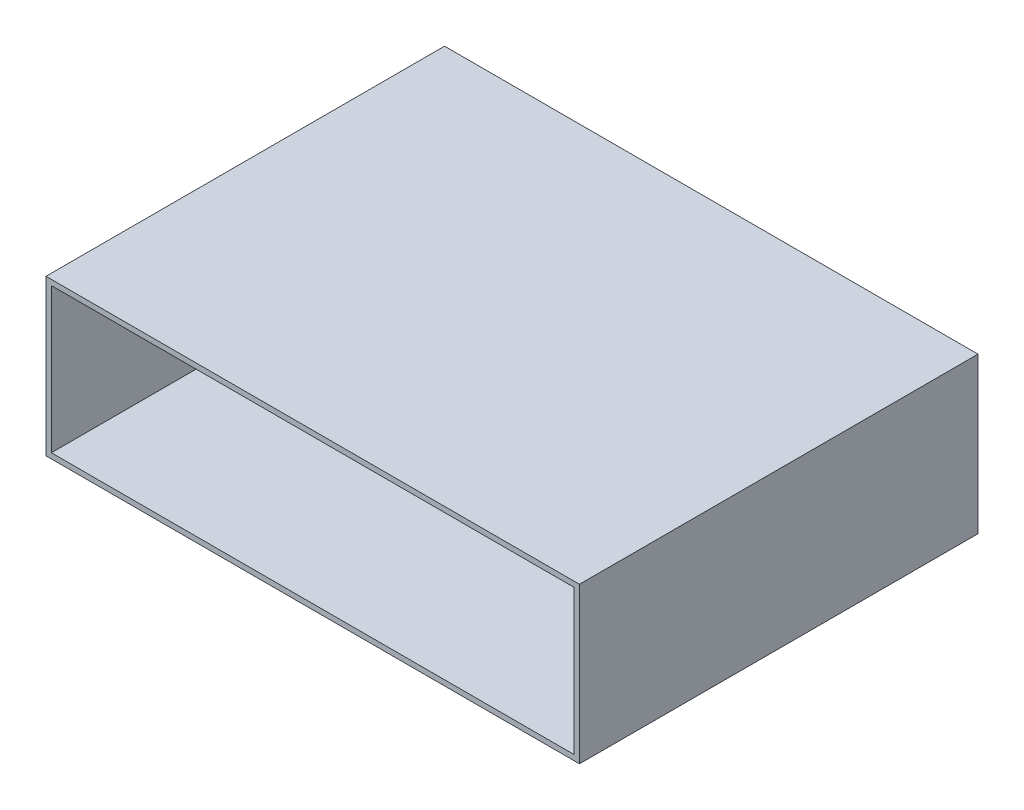
SolidWorks part; units mm, degrees
material "Custom Plastic"
ref_plane "X-Y Datum" through (0, 0, 0) normal (0, 0, 1) x (1, 0, 0)
ref_plane "X-Z Datum" through (0, 0, 0) normal (0, 1, 0) x (1, 0, 0)
ref_plane "Y-Z Datum" through (0, 0, 0) normal (1, 0, 0) x (0, 0, -1)
sketch "Sketch1" plane through (0, 0, 0) normal (0, 0, 1) x (1, 0, 0)
  line L1 (-154.6125, -42.825) -> (154.6125, -42.825)
  line L2 (-154.6125, -42.825) -> (-154.6125, 42.825)
  line L3 (-154.6125, 42.825) -> (154.6125, 42.825)
  line L4 (154.6125, -42.825) -> (154.6125, 42.825)
  line L5 (-154.6125, -42.825) -> (154.6125, 42.825) construction
  line L6 (-154.6125, 42.825) -> (154.6125, -42.825) construction
  line L7 (-157.7875, -46) -> (157.7875, -46)
  line L8 (-157.7875, -46) -> (-157.7875, 46)
  line L9 (-157.7875, 46) -> (157.7875, 46)
  line L10 (157.7875, -46) -> (157.7875, 46)
  line L11 (-157.7875, -46) -> (157.7875, 46) construction
  line L12 (-157.7875, 46) -> (157.7875, -46) construction
  point P0 (0, 0)
  point P6 (0, 0)
  dimension "D1" = 3.175
  dimension "D2" = 3.175
  dimension "D3" = 315.575
  dimension "D4" = 92
extrude "Boss-Extrude1" add sketch "Sketch1" along normal blind 235.775
extrude "Boss-Extrude2" add sketch "Sketch1<2>" along normal blind 3.175 contours L1 L4 L3 L2 region at (0, 0, 0)
sketch "Sketch1<2>" plane through (0, 0, 0) normal (0, 0, 1) x (1, 0, 0) same geometry as "Sketch1"
sketch "Sketch3" plane through (0, 42.825, 0) normal (0, -1, 0) x (1, 0, 0)
  line L0 (0, 0) -> (0, 127)
  line L1 (157.7875, 127) -> (-157.7875, 127)
  line L2 (157.7875, 235.775) -> (157.7875, 0) construction
  line L3 (-157.7875, 235.775) -> (-157.7875, 0) construction
  line L4 (17.6715, 0) -> (17.6715, 88.9)
  line L5 (155.4063, 88.9) -> (-155.4062, 88.9)
  dimension "D1" = 127
  dimension "D2" = 88.9
